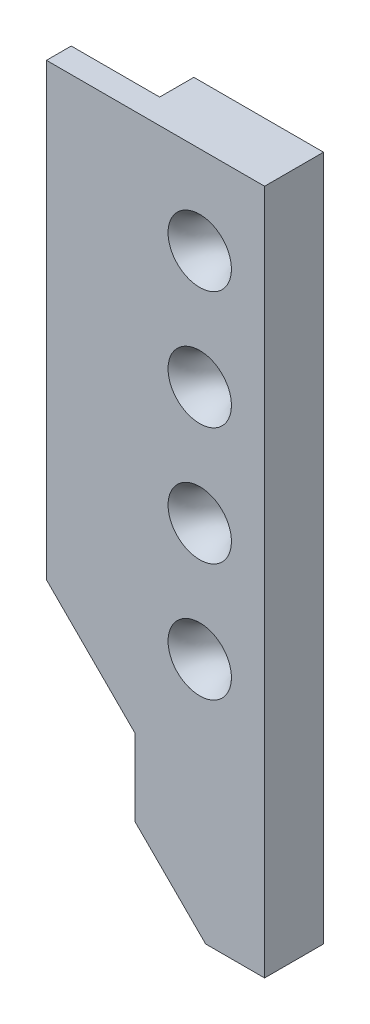
SolidWorks part; units mm, degrees
ref_plane "Front Plane" through (0, 0, 0) normal (0, 0, 1) x (1, 0, 0)
ref_plane "Top Plane" through (0, 0, 0) normal (0, 1, 0) x (1, 0, 0)
ref_plane "Right Plane" through (0, 0, 0) normal (1, 0, 0) x (0, 0, -1)
sketch "Sketch1" plane through (0, 0, 0) normal (0, 0, 1) x (1, 0, 0)
  line L0 (25.2, 31.3209) -> (25.2, -45)
  line L1 (25.2, -45) -> (40.2, -60)
  line L2 (40.2, -60) -> (40.2, 0) construction
  line L3 (40.2, -60) -> (40.2, -85)
  line L5 (62.2, -85) -> (62.2, 31.3209)
  line L6 (62.2, 31.3209) -> (25.2, 31.3209)
  line L12 (40.2, -85) -> (62.2, -85)
  line L13 (40.2, -60) -> (40.2, 31.3209)
  circle A0 centre (0, 0) radius 40.2 construction
  dimension "D1" = 80.4
  dimension "D2" = 15
  dimension "D3" = 15
  dimension "D4" = 60
  dimension "D5" = 25
  dimension "D6" = 22
extrude "Boss-Extrude1" add sketch "Sketch1" along normal blind 4.2 contours L1 L13 L6 L0 | L13 L3 L12 L5 L6 region at (32.9237, -10.7014, 0) region at (51.2, -26.8395, 0)
extrude "Boss-Extrude2" add sketch "Sketch1<3>" against normal blind 5.8 contours L13 L3 L12 L5 L6 region at (51.2, -26.8395, 0)
sketch "Sketch1<3>" plane through (0, 0, 0) normal (0, 0, 1) x (1, 0, 0) same geometry as "Sketch1"
sketch "Sketch2" plane through (0, 0, 4.2) normal (0, 0, 1) x (1, 0, 0)
  line L1 (40.2, -85) -> (62.2, -85) construction
  line L2 (62.2, 31.3209) -> (25.2, 31.3209) construction
  circle A0 centre (51.2, 16.3209) radius 3.375
  point P5 (51.2, -85)
  dimension "D1" = 6.75
  dimension "D2" = 15
extrude "Cut-Extrude1" cut sketch "Sketch2" against normal up to next
ref_axis "Axis1" through (51.2, 16.3209, -5.8) along (0, 0, 1)
ref_plane "Plane1" through (51.2, 0, 0) normal (-1, 0, 0) x (0, 0, 1)
sketch "Sketch3" plane through (51.2, 0, 0) normal (-1, 0, 0) x (0, 0, 1)
  line L0 (4.2, 31.3209) -> (4.2, -45) construction
  line L1 (-5.8, -85) -> (-5.8, 31.3209) construction
  circle A0 centre (-3.8, 19.8959) radius 0.65
  circle A1 centre (2.2, 19.8959) radius 0.65
  dimension "D1" = 1.3
  dimension "D3" = 2
  dimension "D4" = 2
  dimension "D2" = 0.2
pattern_linear "LPattern1" count 4 spacing 20 along (0, -1, 0) of "Cut-Extrude1"
sketch "Sketch4" plane through (0, 0, 4.2) normal (0, 0, 1) x (1, 0, 0)
  line L0 (52.2, -85) -> (40.2, -73)
  line L1 (40.2, -85) -> (62.2, -85) construction
  line L2 (40.2, -85) -> (40.2, -60) construction
  line L3 (40.2, -73) -> (40.2, -85)
  line L4 (40.2, -85) -> (52.2, -85)
  dimension "D1" = 10
  dimension "D2" = 45
extrude "Cut-Extrude2" cut sketch "Sketch4" against normal up to next
ref_plane "Plane2" through (25.2, -45, 0) normal (0, -1, 0) x (-1, 0, 0)
sketch "Sketch6" plane through (25.2, 0, 0) normal (-1, 0, 0) x (0, 0, 1)
  line L0 (4.2, -45) -> (0, -45)
  line L1 (-20.9883, -45) -> (20.9883, -45) construction
  line L2 (4.2, -45) -> (4.2, -60) construction
  line L3 (0, -45) -> (3.7, -60)
  line L4 (4.2, -60) -> (0, -60) construction
  line L5 (3.7, -60) -> (4.2, -60)
  line L6 (4.2, -60) -> (4.2, -45)
  line L8 (4.2, -45) -> (0, -45)
  line L9 (4.2, -45) -> (4.2, -60)
  line L10 (4.2, -60) -> (0, -60)
  line L11 (0, -45) -> (0, -60)
  dimension "D1" = 0.5
extrude "Cut-Extrude3" cut sketch "Sketch6" against normal up to surface (15 mm away) contours L3 L11 L10 region at (25.2, -55, 1.2333) up to face at (40.2, -33.893, -0.5333)
ref_plane "Plane3" through (25.5117, -18.7086, 0) normal (0.8064, -0.5914, 0) x (0, 0, -1)
sketch "Sketch9" plane through (25.5117, -18.7086, 0) normal (0.8064, -0.5914, 0) x (0, 0, -1)
  line L1 (-2.8, 46.8141) -> (-0.6, 46.8141) construction
  line L2 (5.8, 46.8141) -> (-4.2, 46.8141) construction
  line L3 (-4.2, -31.7616) -> (-4.2, 62.0402) construction
  line L5 (-2.9, 47.2937) -> (-0.5, 47.2937) construction
  line L6 (-0.5, 47.2937) -> (-2.9, 47.2937)
  arc A0 (-2.9, 47.2937) -> (-0.5, 47.2937) centre (-1.7, 47.2937) ccw
  point P11 (-1.7, 47.2937)
  dimension "D1" = 2.4
  dimension "D2" = 2.2
  dimension "D3" = 2.5
revolve "Cut-Revolve4" [suppressed] cut sketch "Sketch9" angle 360 about L6
pattern_circular "CirPattern1" [suppressed] count 4 over 360 about axis through (51.2, 16.3209, -5.8) along (0, 0, 1) of bodies 108
pattern_linear "LPattern2" [suppressed] count 4 spacing 20 count 2 spacing 5 of bodies 109
sketch "Sketch10" plane through (51.2, 0, 0) normal (-1, 0, 0) x (0, 0, 1)
  line L0 (-5.8, -73) -> (-5.8, 31.3209) construction
  line L1 (4.2, 31.3209) -> (4.2, -45) construction
  line L2 (4.2, 21.6959) -> (4.2, 19.6959)
  line L3 (4.2, 19.6959) -> (-5.8, 19.6959)
  line L4 (-5.8, 19.6959) -> (-5.8, 21.6959)
  arc A0 (-5.8, 21.6959) -> (4.2, 21.6959) centre (-0.8, 26.9459) ccw
  dimension "D1" = 2
revolve "Cut-Revolve5" cut sketch "Sketch10" angle 360 about axis through (51.2, 16.3209, -5.8) along (0, 0, 1) region at (51.2, 20.2785, -4.5871) region at (51.2, 20.2785, 2.9871)
pattern_linear "LPattern3" count 4 spacing 20 along (0, -1, 0) of "Cut-Revolve5"
